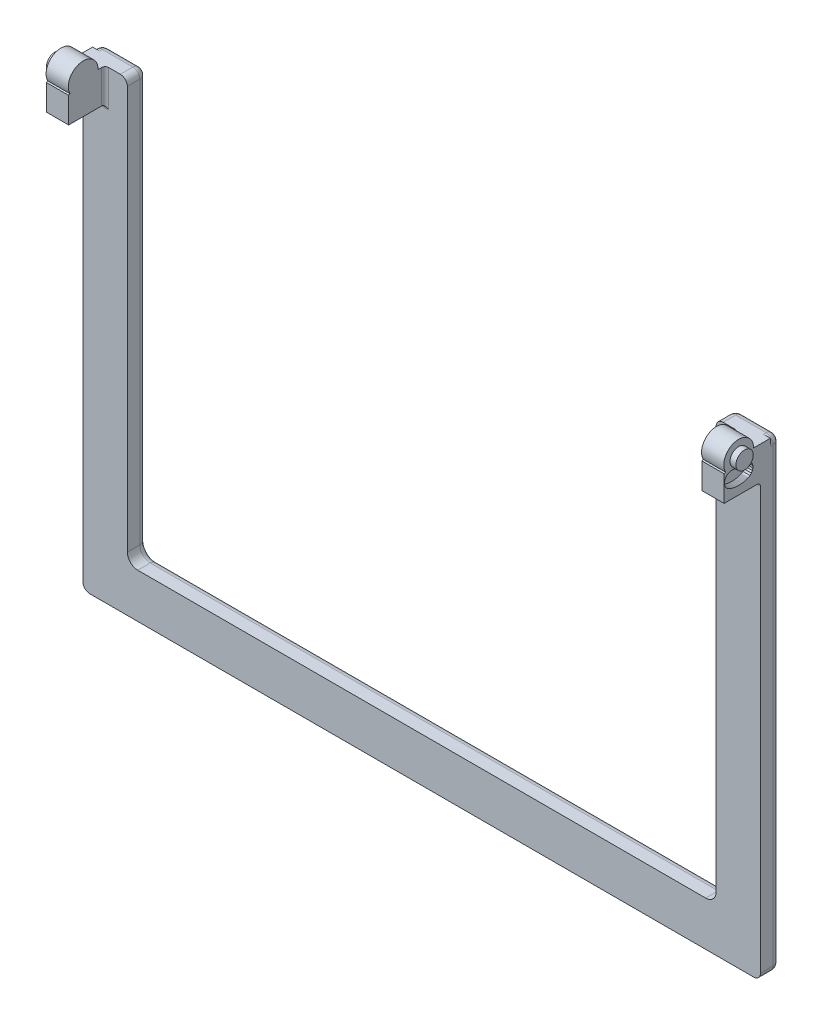
SolidWorks part; units mm, degrees
ref_plane "Спереди" through (0, 0, 0) normal (0, 0, 1) x (1, 0, 0)
ref_plane "Сверху" through (0, 0, 0) normal (0, 1, 0) x (1, 0, 0)
ref_plane "Справа" through (0, 0, 0) normal (1, 0, 0) x (0, 0, -1)
other "Configuration Table"
sketch "Left_leg_profile" plane through (0, 0, 0) normal (0, 0, 1) x (1, 0, 0)
  line L0 (-0.6, -6.6) -> (8.2, -6.6)
  line L1 (10.2, -4.6) -> (10.2, 123)
  line L2 (8.2, 125) -> (-0.6, 125)
  line L3 (-2.6, 123) -> (-2.6, -4.6)
  arc A0 (8.2, -6.6) -> (10.2, -4.6) centre (8.2, -4.6) ccw
  arc A1 (10.2, 123) -> (8.2, 125) centre (8.2, 123) ccw
  arc A2 (-0.6, 125) -> (-2.6, 123) centre (-0.6, 123) ccw
  arc A3 (-2.6, -4.6) -> (-0.6, -6.6) centre (-0.6, -4.6) ccw
extrude "Left_leg" add sketch "Left_leg_profile" along normal blind 5.6 from offset 18.1 offset against normal yes
sketch "Foot_crossbar_profile" plane through (0, 0, 0) normal (0, 0, 1) x (1, 0, 0)
  line L0 (-0.6, -9) -> (190.6, -9)
  line L1 (192.6, -7) -> (192.6, 1.8)
  line L2 (190.6, 3.8) -> (-0.6, 3.8)
  line L3 (-2.6, 1.8) -> (-2.6, -7)
  arc A0 (190.6, -9) -> (192.6, -7) centre (190.6, -7) ccw
  arc A1 (192.6, 1.8) -> (190.6, 3.8) centre (190.6, 1.8) ccw
  arc A2 (-0.6, 3.8) -> (-2.6, 1.8) centre (-0.6, 1.8) ccw
  arc A3 (-2.6, -7) -> (-0.6, -9) centre (-0.6, -7) ccw
extrude "Foot_crossbar" add sketch "Foot_crossbar_profile" along normal blind 5.6 from offset 18.1 offset against normal yes
sketch "Right_leg_profile" plane through (0, 0, 0) normal (0, 0, 1) x (1, 0, 0)
  line L0 (181.8, -6.6) -> (190.6, -6.6)
  line L1 (192.6, -4.6) -> (192.6, 123)
  line L2 (190.6, 125) -> (181.8, 125)
  line L3 (179.8, 123) -> (179.8, -4.6)
  arc A0 (190.6, -6.6) -> (192.6, -4.6) centre (190.6, -4.6) ccw
  arc A1 (192.6, 123) -> (190.6, 125) centre (190.6, 123) ccw
  arc A2 (181.8, 125) -> (179.8, 123) centre (181.8, 123) ccw
  arc A3 (179.8, -4.6) -> (181.8, -6.6) centre (181.8, -4.6) ccw
extrude "Right_leg" add sketch "Right_leg_profile" along normal blind 5.6 from offset 18.1 offset against normal yes
sketch "Pivot_neck_0_profile" plane through (0, 0, 0) normal (1, 0, 0) x (0, 0, -1)
  line L0 (15.3, 115.4) -> (15.3, 125)
  line L1 (15.3, 125) -> (6.2, 125)
  line L2 (6.2, 125) -> (2, 122.8)
  line L3 (2, 122.8) -> (2, 115.4)
  line L4 (2, 115.4) -> (15.3, 115.4)
extrude "Pivot_neck_0" add sketch "Pivot_neck_0_profile" along normal blind 6.4 from offset 2.6 offset against normal yes
sketch "Pivot_lug_0_profile" plane through (0, 0, 0) normal (1, 0, 0) x (0, 0, -1)
  circle A0 centre (6.2, 125) radius 4.3
extrude "Pivot_lug_0" add sketch "Pivot_lug_0_profile" along normal blind 6.4 from offset 2.6 offset against normal yes
sketch "Captive_axle_0_profile" plane through (0, 0, 0) normal (1, 0, 0) x (0, 0, -1)
  circle A0 centre (6.2, 125) radius 2.5
extrude "Captive_axle_0" add sketch "Captive_axle_0_profile" along normal blind 2 from offset 4.3 offset against normal yes
sketch "Blind_rotation_groove_0_profile" plane through (0, 0, 0) normal (1, 0, 0) x (0, 0, -1)
  line L0 (8.9553, 118.3481) -> (8.7362, 118.2615)
  line L1 (8.7362, 118.2615) -> (8.5144, 118.1821)
  line L2 (8.5144, 118.1821) -> (8.29, 118.11)
  line L3 (8.29, 118.11) -> (8.0635, 118.0453)
  line L4 (8.0635, 118.0453) -> (7.8349, 117.9881)
  line L5 (7.8349, 117.9881) -> (7.6047, 117.9383)
  line L6 (7.6047, 117.9383) -> (7.3728, 117.8962)
  line L7 (7.3728, 117.8962) -> (7.1398, 117.8616)
  line L8 (7.1398, 117.8616) -> (6.9057, 117.8347)
  line L9 (6.9057, 117.8347) -> (6.6709, 117.8154)
  line L10 (6.6709, 117.8154) -> (6.4356, 117.8039)
  line L11 (6.4356, 117.8039) -> (6.2, 117.8)
  line L12 (6.2, 117.8) -> (5.9644, 117.8039)
  line L13 (5.9644, 117.8039) -> (5.7291, 117.8154)
  line L14 (5.7291, 117.8154) -> (5.4943, 117.8347)
  line L15 (5.4943, 117.8347) -> (5.2602, 117.8616)
  line L16 (5.2602, 117.8616) -> (5.0272, 117.8962)
  line L17 (5.0272, 117.8962) -> (4.7953, 117.9383)
  line L18 (4.7953, 117.9383) -> (4.5651, 117.9881)
  line L19 (4.5651, 117.9881) -> (4.3365, 118.0453)
  line L20 (4.3365, 118.0453) -> (4.11, 118.11)
  line L21 (4.11, 118.11) -> (3.8856, 118.1821)
  line L22 (3.8856, 118.1821) -> (3.6638, 118.2615)
  line L23 (3.6638, 118.2615) -> (3.4447, 118.3481)
  line L24 (3.4447, 118.3481) -> (2.9473, 118.6352)
  line L25 (2.9473, 118.6352) -> (2.5412, 119.0413)
  line L26 (2.5412, 119.0413) -> (2.254, 119.5387)
  line L27 (2.254, 119.5387) -> (2.1054, 120.0934)
  line L28 (2.1054, 120.0934) -> (2.1054, 120.6678)
  line L29 (2.1054, 120.6678) -> (2.254, 121.2225)
  line L30 (2.254, 121.2225) -> (2.5412, 121.7199)
  line L31 (2.5412, 121.7199) -> (2.9473, 122.126)
  line L32 (2.9473, 122.126) -> (3.4447, 122.4131)
  line L33 (3.4447, 122.4131) -> (3.9994, 122.5618)
  line L34 (3.9994, 122.5618) -> (4.5737, 122.5618)
  line L35 (4.5737, 122.5618) -> (5.1285, 122.4131)
  line L36 (5.1285, 122.4131) -> (5.2137, 122.3795)
  line L37 (5.2137, 122.3795) -> (5.3, 122.3486)
  line L38 (5.3, 122.3486) -> (5.3872, 122.3206)
  line L39 (5.3872, 122.3206) -> (5.4753, 122.2954)
  line L40 (5.4753, 122.2954) -> (5.5642, 122.2731)
  line L41 (5.5642, 122.2731) -> (5.6537, 122.2538)
  line L42 (5.6537, 122.2538) -> (5.7439, 122.2374)
  line L43 (5.7439, 122.2374) -> (5.8345, 122.224)
  line L44 (5.8345, 122.224) -> (5.9256, 122.2135)
  line L45 (5.9256, 122.2135) -> (6.0169, 122.206)
  line L46 (6.0169, 122.206) -> (6.1084, 122.2015)
  line L47 (6.1084, 122.2015) -> (6.2, 122.2)
  line L48 (6.2, 122.2) -> (6.2916, 122.2015)
  line L49 (6.2916, 122.2015) -> (6.3831, 122.206)
  line L50 (6.3831, 122.206) -> (6.4744, 122.2135)
  line L51 (6.4744, 122.2135) -> (6.5655, 122.224)
  line L52 (6.5655, 122.224) -> (6.6561, 122.2374)
  line L53 (6.6561, 122.2374) -> (6.7463, 122.2538)
  line L54 (6.7463, 122.2538) -> (6.8358, 122.2731)
  line L55 (6.8358, 122.2731) -> (6.9247, 122.2954)
  line L56 (6.9247, 122.2954) -> (7.0128, 122.3206)
  line L57 (7.0128, 122.3206) -> (7.1, 122.3486)
  line L58 (7.1, 122.3486) -> (7.1863, 122.3795)
  line L59 (7.1863, 122.3795) -> (7.2715, 122.4131)
  line L60 (7.2715, 122.4131) -> (7.8263, 122.5618)
  line L61 (7.8263, 122.5618) -> (8.4006, 122.5618)
  line L62 (8.4006, 122.5618) -> (8.9553, 122.4131)
  line L63 (8.9553, 122.4131) -> (9.4527, 122.126)
  line L64 (9.4527, 122.126) -> (9.8588, 121.7199)
  line L65 (9.8588, 121.7199) -> (10.146, 121.2225)
  line L66 (10.146, 121.2225) -> (10.2946, 120.6678)
  line L67 (10.2946, 120.6678) -> (10.2946, 120.0934)
  line L68 (10.2946, 120.0934) -> (10.146, 119.5387)
  line L69 (10.146, 119.5387) -> (9.8588, 119.0413)
  line L70 (9.8588, 119.0413) -> (9.4527, 118.6352)
  line L71 (9.4527, 118.6352) -> (8.9553, 118.3481)
extrude "Blind_rotation_groove_0" cut sketch "Blind_rotation_groove_0_profile" along normal blind 2.1 from offset 2.7 offset against normal yes
sketch "Pivot_neck_1_profile" plane through (0, 0, 0) normal (1, 0, 0) x (0, 0, -1)
  line L0 (15.3, 115.4) -> (15.3, 125)
  line L1 (15.3, 125) -> (6.2, 125)
  line L2 (6.2, 125) -> (2, 122.8)
  line L3 (2, 122.8) -> (2, 115.4)
  line L4 (2, 115.4) -> (15.3, 115.4)
extrude "Pivot_neck_1" add sketch "Pivot_neck_1_profile" along normal blind 6.4 from offset 186.2
sketch "Pivot_lug_1_profile" plane through (0, 0, 0) normal (1, 0, 0) x (0, 0, -1)
  circle A0 centre (6.2, 125) radius 4.3
extrude "Pivot_lug_1" add sketch "Pivot_lug_1_profile" along normal blind 6.4 from offset 186.2
sketch "Captive_axle_1_profile" plane through (0, 0, 0) normal (1, 0, 0) x (0, 0, -1)
  circle A0 centre (6.2, 125) radius 2.5
extrude "Captive_axle_1" add sketch "Captive_axle_1_profile" along normal blind 2 from offset 192.3
sketch "Blind_rotation_groove_1_profile" plane through (0, 0, 0) normal (1, 0, 0) x (0, 0, -1)
  line L0 (8.9553, 118.3481) -> (8.7362, 118.2615)
  line L1 (8.7362, 118.2615) -> (8.5144, 118.1821)
  line L2 (8.5144, 118.1821) -> (8.29, 118.11)
  line L3 (8.29, 118.11) -> (8.0635, 118.0453)
  line L4 (8.0635, 118.0453) -> (7.8349, 117.9881)
  line L5 (7.8349, 117.9881) -> (7.6047, 117.9383)
  line L6 (7.6047, 117.9383) -> (7.3728, 117.8962)
  line L7 (7.3728, 117.8962) -> (7.1398, 117.8616)
  line L8 (7.1398, 117.8616) -> (6.9057, 117.8347)
  line L9 (6.9057, 117.8347) -> (6.6709, 117.8154)
  line L10 (6.6709, 117.8154) -> (6.4356, 117.8039)
  line L11 (6.4356, 117.8039) -> (6.2, 117.8)
  line L12 (6.2, 117.8) -> (5.9644, 117.8039)
  line L13 (5.9644, 117.8039) -> (5.7291, 117.8154)
  line L14 (5.7291, 117.8154) -> (5.4943, 117.8347)
  line L15 (5.4943, 117.8347) -> (5.2602, 117.8616)
  line L16 (5.2602, 117.8616) -> (5.0272, 117.8962)
  line L17 (5.0272, 117.8962) -> (4.7953, 117.9383)
  line L18 (4.7953, 117.9383) -> (4.5651, 117.9881)
  line L19 (4.5651, 117.9881) -> (4.3365, 118.0453)
  line L20 (4.3365, 118.0453) -> (4.11, 118.11)
  line L21 (4.11, 118.11) -> (3.8856, 118.1821)
  line L22 (3.8856, 118.1821) -> (3.6638, 118.2615)
  line L23 (3.6638, 118.2615) -> (3.4447, 118.3481)
  line L24 (3.4447, 118.3481) -> (2.9473, 118.6352)
  line L25 (2.9473, 118.6352) -> (2.5412, 119.0413)
  line L26 (2.5412, 119.0413) -> (2.254, 119.5387)
  line L27 (2.254, 119.5387) -> (2.1054, 120.0934)
  line L28 (2.1054, 120.0934) -> (2.1054, 120.6678)
  line L29 (2.1054, 120.6678) -> (2.254, 121.2225)
  line L30 (2.254, 121.2225) -> (2.5412, 121.7199)
  line L31 (2.5412, 121.7199) -> (2.9473, 122.126)
  line L32 (2.9473, 122.126) -> (3.4447, 122.4131)
  line L33 (3.4447, 122.4131) -> (3.9994, 122.5618)
  line L34 (3.9994, 122.5618) -> (4.5737, 122.5618)
  line L35 (4.5737, 122.5618) -> (5.1285, 122.4131)
  line L36 (5.1285, 122.4131) -> (5.2137, 122.3795)
  line L37 (5.2137, 122.3795) -> (5.3, 122.3486)
  line L38 (5.3, 122.3486) -> (5.3872, 122.3206)
  line L39 (5.3872, 122.3206) -> (5.4753, 122.2954)
  line L40 (5.4753, 122.2954) -> (5.5642, 122.2731)
  line L41 (5.5642, 122.2731) -> (5.6537, 122.2538)
  line L42 (5.6537, 122.2538) -> (5.7439, 122.2374)
  line L43 (5.7439, 122.2374) -> (5.8345, 122.224)
  line L44 (5.8345, 122.224) -> (5.9256, 122.2135)
  line L45 (5.9256, 122.2135) -> (6.0169, 122.206)
  line L46 (6.0169, 122.206) -> (6.1084, 122.2015)
  line L47 (6.1084, 122.2015) -> (6.2, 122.2)
  line L48 (6.2, 122.2) -> (6.2916, 122.2015)
  line L49 (6.2916, 122.2015) -> (6.3831, 122.206)
  line L50 (6.3831, 122.206) -> (6.4744, 122.2135)
  line L51 (6.4744, 122.2135) -> (6.5655, 122.224)
  line L52 (6.5655, 122.224) -> (6.6561, 122.2374)
  line L53 (6.6561, 122.2374) -> (6.7463, 122.2538)
  line L54 (6.7463, 122.2538) -> (6.8358, 122.2731)
  line L55 (6.8358, 122.2731) -> (6.9247, 122.2954)
  line L56 (6.9247, 122.2954) -> (7.0128, 122.3206)
  line L57 (7.0128, 122.3206) -> (7.1, 122.3486)
  line L58 (7.1, 122.3486) -> (7.1863, 122.3795)
  line L59 (7.1863, 122.3795) -> (7.2715, 122.4131)
  line L60 (7.2715, 122.4131) -> (7.8263, 122.5618)
  line L61 (7.8263, 122.5618) -> (8.4006, 122.5618)
  line L62 (8.4006, 122.5618) -> (8.9553, 122.4131)
  line L63 (8.9553, 122.4131) -> (9.4527, 122.126)
  line L64 (9.4527, 122.126) -> (9.8588, 121.7199)
  line L65 (9.8588, 121.7199) -> (10.146, 121.2225)
  line L66 (10.146, 121.2225) -> (10.2946, 120.6678)
  line L67 (10.2946, 120.6678) -> (10.2946, 120.0934)
  line L68 (10.2946, 120.0934) -> (10.146, 119.5387)
  line L69 (10.146, 119.5387) -> (9.8588, 119.0413)
  line L70 (9.8588, 119.0413) -> (9.4527, 118.6352)
  line L71 (9.4527, 118.6352) -> (8.9553, 118.3481)
extrude "Blind_rotation_groove_1" cut sketch "Blind_rotation_groove_1_profile" along normal blind 2.1 from offset 190.6
fillet "Stand_leg_root_round" radius 3 2 edges at (10.2, 3.8, -15.3) (179.8, 3.8, -15.3)
fillet "Pivot_neck_root_round" radius 1 4 edges at (0.6, 115.4, -12.5) (3.8, 120.2, -12.5) (189.4, 115.4, -12.5) (186.2, 120.2, -12.5)
fillet "Stand_contact_round" radius 2 16 edges at (-2.0142, 124.4142, -18.1) (192.0142, 124.4142, -18.1) (3.8, 125, -18.1) (9.6142, 124.4142, -18.1) (-2.6, 58, -18.1) (10.2, 64.9, -18.1) (-2.0142, -8.4142, -18.1) (11.0787, 4.6787, -18.1) (95, -9, -18.1) (95, 3.8, -18.1) (192.0142, -8.4142, -18.1) (178.9213, 4.6787, -18.1) (192.6, 58, -18.1) (179.8, 64.9, -18.1) (180.3858, 124.4142, -18.1) (186.2, 125, -18.1)
